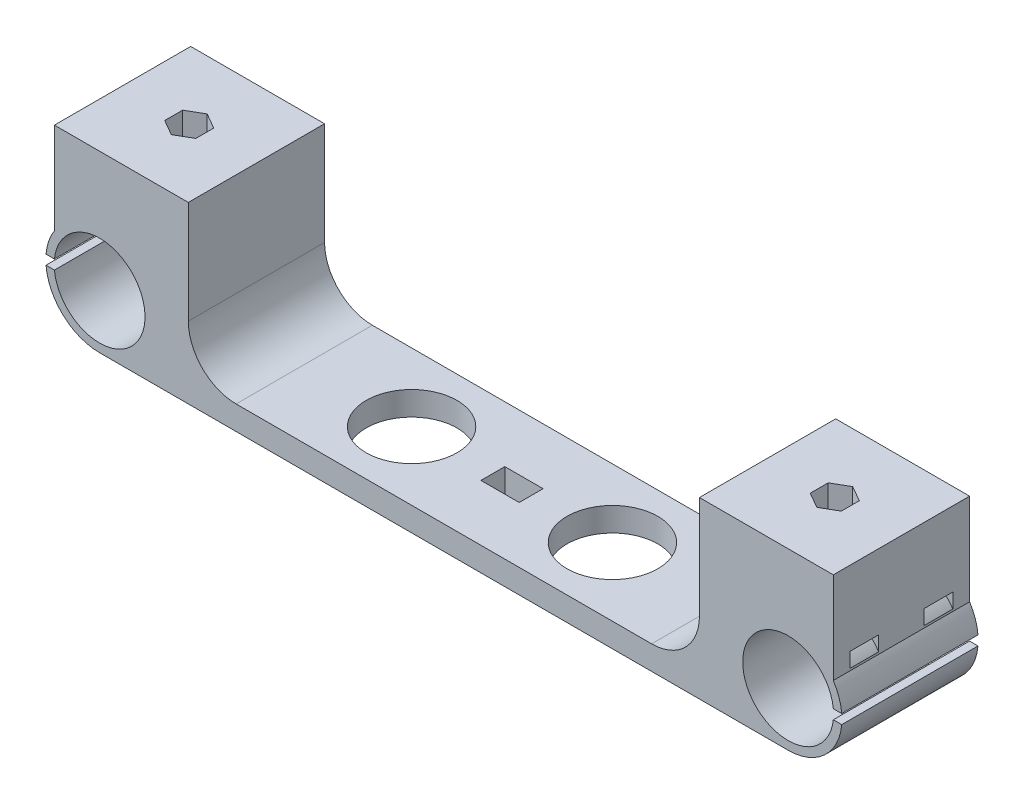
SolidWorks part; units mm, degrees
ref_plane "Front Plane" through (0, 0, 0) normal (0, 0, 1) x (1, 0, 0)
ref_plane "Top Plane" through (0, 0, 0) normal (0, 1, 0) x (1, 0, 0)
ref_plane "Right Plane" through (0, 0, 0) normal (1, 0, 0) x (0, 0, -1)
sketch "Sketch7" plane through (0, 0, 0) normal (0, 0, 1) x (1, 0, 0)
  line L0 (-29.0092, -3.4353) -> (114.9908, -3.4353)
  line L1 (-10.4565, 1.5647) -> (96.438, 1.5647)
  line L8 (126.1962, 6.8147) -> (124.438, 6.8147)
  line L9 (126.1962, 8.8147) -> (124.438, 8.8147)
  line L10 (42.9908, -3.4353) -> (42.9908, 54.826) construction
  line L11 (-40.2147, 8.8147) -> (-38.4565, 8.8147)
  line L12 (-40.2147, 6.8147) -> (-38.4565, 6.8147)
  line L19 (-38.4565, 13.9231) -> (-38.4565, 33.0647)
  line L20 (-38.4565, 33.0647) -> (-10.4565, 33.0647)
  line L21 (-10.4565, 33.0647) -> (-10.4565, 1.5647)
  line L22 (96.438, 33.0647) -> (96.438, 1.5647)
  line L23 (124.438, 13.9231) -> (124.438, 33.0647)
  line L24 (124.438, 33.0647) -> (96.438, 33.0647)
  arc A0 (124.438, 8.8147) -> (124.438, 6.8147) centre (114.9908, 7.8147) ccw
  arc A1 (-38.4565, 6.8147) -> (-38.4565, 8.8147) centre (-29.0092, 7.8147) ccw
  arc A2 (114.9908, -3.4353) -> (126.1962, 6.8147) centre (114.9908, 7.8147) ccw
  arc A3 (-38.4565, 13.9231) -> (-40.2147, 8.8147) centre (-29.0092, 7.8147) ccw
  arc A4 (-40.2147, 6.8147) -> (-29.0092, -3.4353) centre (-29.0092, 7.8147) ccw
  arc A5 (126.1962, 8.8147) -> (124.438, 13.9231) centre (114.9908, 7.8147) ccw
  dimension "D2" = 19
  dimension "D3" = 1.75
  dimension "D11" = 28
  dimension "D5" = 2
  dimension "D1" = 144
  dimension "D4" = 5
  dimension "D6" = 1
  dimension "D12" = 31.5
extrude "Boss-Extrude3" add sketch "Sketch7" along normal blind 28.5
fillet "Fillet1" radius 10 2 edges at (96.438, 1.5647, 14.25) (-10.4565, 1.5647, 14.25)
sketch "Sketch8" plane through (0, 1.5647, 0) normal (0, 1, 0) x (1, 0, 0)
  line L0 (42.9908, 0) -> (42.9908, -28.5) construction
  line L1 (86.438, 0) -> (-0.4565, 0) construction
  line L2 (86.438, -28.5) -> (-0.4565, -28.5) construction
  line L3 (86.438, -14.25) -> (-0.4565, -14.25) construction
  line L4 (38.9908, -11.75) -> (46.9908, -11.75)
  line L5 (38.9908, -11.75) -> (38.9908, -16.75)
  line L6 (38.9908, -16.75) -> (46.9908, -16.75)
  line L7 (46.9908, -11.75) -> (46.9908, -16.75)
  line L8 (86.438, -28.5) -> (86.438, 0) construction
  line L9 (-0.4565, 0) -> (-0.4565, -28.5) construction
  circle A0 centre (63.9908, -14.25) radius 9.5
  circle A1 centre (21.9908, -14.25) radius 9.5
  dimension "D5" = 19
  dimension "D7" = 21
  dimension "D1" = 5
  dimension "D2" = 8
  dimension "D3" = 4
  dimension "D4" = 2.5
  dimension "D6" = 21
extrude "Cut-Extrude4" cut sketch "Sketch8" against normal up to surface (5 mm away) up to face at (42.9908, -3.4353, 14.25)
sketch "Sketch10" plane through (0, 33.0647, 0) normal (0, 1, 0) x (1, 0, 0)
  line L0 (124.438, -14.25) -> (-38.4565, -14.25) construction
  line L1 (124.438, -28.5) -> (124.438, 0) construction
  line L2 (-38.4565, -28.5) -> (-38.4565, 0) construction
  line L3 (110.4908, 0) -> (110.4908, -28.5) construction
  line L4 (124.438, 0) -> (96.438, 0) construction
  line L5 (124.438, -28.5) -> (96.438, -28.5) construction
  line L6 (-24.5092, 0) -> (-24.5092, -28.5) construction
  line L7 (-10.4565, 0) -> (-38.4565, 0) construction
  line L8 (-10.4565, -28.5) -> (-38.4565, -28.5) construction
  line L9 (86.438, 0) -> (-0.4565, 0) construction
  circle A0 centre (110.4908, -14.25) radius 1.75
  circle A1 centre (-24.5092, -14.25) radius 1.75
  point P30 (42.9908, 0)
  dimension "D1" = 3.5
  dimension "D2" = 135
  dimension "D3" = 67.5
extrude "Cut-Extrude6" cut sketch "Sketch10" against normal blind 10
sketch "Sketch13" plane through (0, 33.0647, 0) normal (0, 1, 0) x (1, 0, 0)
  line L1 (107.2408, -12.3736) -> (107.2408, -16.1264)
  line L2 (107.2408, -16.1264) -> (110.4908, -18.0028)
  line L3 (110.4908, -18.0028) -> (113.7408, -16.1264)
  line L4 (113.7408, -16.1264) -> (113.7408, -12.3736)
  line L5 (113.7408, -12.3736) -> (110.4908, -10.4972)
  line L6 (110.4908, -10.4972) -> (107.2408, -12.3736)
  line L7 (-24.5092, -18.0028) -> (-21.2592, -16.1264)
  line L8 (-21.2592, -16.1264) -> (-21.2592, -12.3736)
  line L9 (-21.2592, -12.3736) -> (-24.5092, -10.4972)
  line L10 (-24.5092, -10.4972) -> (-27.7592, -12.3736)
  line L11 (-27.7592, -12.3736) -> (-27.7592, -16.1264)
  line L12 (-27.7592, -16.1264) -> (-24.5092, -18.0028)
  line L13 (126.1962, -28.5) -> (126.1962, 0) construction
  circle A0 centre (110.4908, -14.25) radius 3.25 construction
  circle A1 centre (-24.5092, -14.25) radius 3.25 construction
  dimension "D1" = 6.5
extrude "Cut-Extrude9" cut sketch "Sketch13" against normal blind 5
ref_axis "Axis2" through (114.9908, 7.8147, 28.5) along (0, 0, -1)
ref_plane "Plane1" through (114.9908, 0, 0) normal (-1, 0, 0) x (0, 0, 1)
sketch "Sketch17" plane through (114.9908, 0, 0) normal (-1, 0, 0) x (0, 0, 1)
  line L1 (25, 19.3147) -> (19, 19.3147)
  line L2 (25, 19.3147) -> (25, 21.3147)
  line L3 (25, 21.3147) -> (19, 21.3147)
  line L4 (19, 19.3147) -> (19, 21.3147)
  line L5 (28.5, 17.3147) -> (0, 17.3147) construction
  line L10 (28.5, 33.0647) -> (28.5, 13.9231) construction
  line L11 (3.5, 21.3147) -> (9.5, 21.3147)
  line L12 (3.5, 21.3147) -> (3.5, 19.3147)
  line L13 (3.5, 19.3147) -> (9.5, 19.3147)
  line L14 (9.5, 21.3147) -> (9.5, 19.3147)
  line L15 (0, 33.0647) -> (0, 13.9231) construction
  dimension "D1" = 2
  dimension "D3" = 2
  dimension "D4" = 6
  dimension "D5" = 3.5
  dimension "D6" = 3.5
revolve "Cut-Revolve1" cut sketch "Sketch17" angle 360 about axis through (114.9908, 7.8147, 28.5) along (0, 0, -1)
sketch "Sketch14" [suppressed] plane through (0, 0, 28) normal (0, 0, 1) x (1, 0, 0)
  line L1 (-82.4893, 23.5071) -> (44.7899, 150.7863)
  line L2 (-82.4893, 23.5071) -> (44.7899, -103.7721)
  line L3 (44.7899, -103.7721) -> (172.0692, 23.5071)
  line L4 (44.7899, 150.7863) -> (172.0692, 23.5071)
  line L6 (124.4774, 32.3147) -> (96.4774, 32.3147) construction
  dimension "D1" = 180
  dimension "D2" = 180
  dimension "D3" = 45
sketch "Sketch11" [suppressed] plane through (0, 0, 28.5) normal (0, 0, 1) x (1, 0, 0)
  line L1 (-81.97, 62.499) -> (96.4919, 62.499)
  line L2 (-81.97, 62.499) -> (-81.97, -13.3564)
  line L3 (-81.97, -13.3564) -> (96.4919, -13.3564)
  line L4 (96.4919, 62.499) -> (96.4919, -13.3564)
extrude "Cut-Extrude7" [suppressed] cut sketch "Sketch11" against normal blind 56
sketch "Sketch15" [suppressed] plane through (96.4919, 0, 0) normal (-1, 0, 0) x (0, 0, 1)
  line L1 (14.4804, 34.5927) -> (32.6535, 34.5927)
  line L2 (14.4804, 34.5927) -> (14.4804, -6.1058)
  line L3 (14.4804, -6.1058) -> (32.6535, -6.1058)
  line L4 (32.6535, 34.5927) -> (32.6535, -6.1058)
extrude "Cut-Extrude10" [suppressed] cut sketch "Sketch15" against normal blind 39
ref_plane "Plane2" through (42.9908, 0, 0) normal (1, 0, 0) x (0, 0, -1)
mirror "Mirror1" about plane through (42.9908, 0, 0) normal (1, 0, 0) of "Cut-Revolve1"
